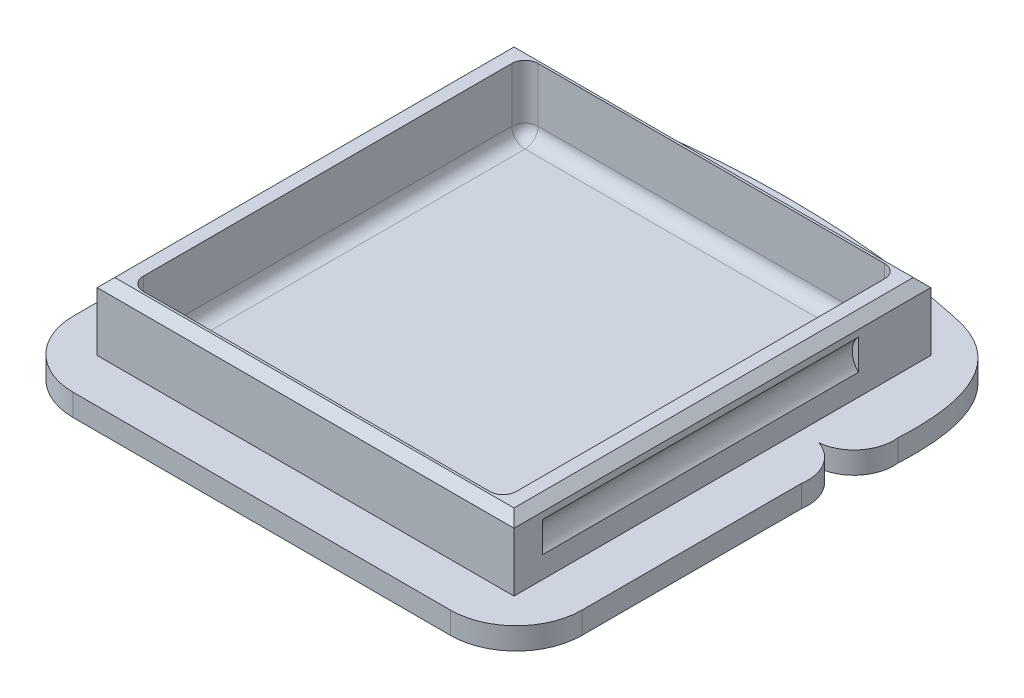
SolidWorks part; units mm, degrees
material "Oak"
ref_plane "Front Plane" through (0, 0, 0) normal (0, 0, 1) x (1, 0, 0)
ref_plane "Top Plane" through (0, 0, 0) normal (0, 1, 0) x (1, 0, 0)
ref_plane "Right Plane" through (0, 0, 0) normal (1, 0, 0) x (0, 0, -1)
sketch "Sketch2" plane through (0, 0, 0) normal (0, 1, 0) x (1, 0, 0)
  line L0 (-66.04, 22.225) -> (66.04, 22.225)
  line L1 (63.5, -66.675) -> (-63.5, -66.675)
  line L2 (63.5, -66.675) -> (63.5, 66.675)
  line L3 (63.5, 66.675) -> (-63.5, 66.675)
  line L4 (-63.5, -66.675) -> (-63.5, 66.675)
  line L5 (63.5, -66.675) -> (-63.5, 66.675) construction
  line L6 (63.5, 66.675) -> (-63.5, -66.675) construction
  line L7 (-73.66, 9.525) -> (-73.66, -53.975)
  line L8 (-54.61, -73.025) -> (54.61, -73.025)
  line L9 (73.66, -53.975) -> (73.66, 9.525)
  line L10 (-73.66, 9.525) -> (-73.66, 13.1711)
  arc A0 (-73.66, 9.525) -> (-66.04, 22.225) centre (-62.3051, 11.348) cw
  arc A1 (73.66, 9.525) -> (66.04, 22.225) centre (62.3051, 11.348) ccw
  arc A2 (-66.04, 22.225) -> (-76.2, 34.925) centre (-64.77, 33.655) cw
  arc A3 (66.04, 22.225) -> (76.2, 34.925) centre (64.77, 33.655) ccw
  arc A4 (-54.2615, 73.3341) -> (54.2615, 73.3341) centre (0, -178.2209) cw
  arc A5 (73.66, -53.975) -> (54.61, -73.025) centre (54.61, -53.975) cw
  arc A6 (-73.66, -53.975) -> (-54.61, -73.025) centre (-54.61, -53.975) ccw
  spline S0 degree 2 poles (-54.2615, 73.3341) (-78.0337, 68.7721) (-76.2, 34.925) knots 0 0 0 1 1 1
  spline S1 degree 2 poles (54.2615, 73.3341) (78.0337, 68.7721) (76.2, 34.925) knots 0 0 0 1 1 1
  point P0 (0, 0)
  dimension "D11" = 11.5003
  dimension "D12" = 11.5003
  dimension "D14" = 11.5003
  dimension "D15" = 11.5003
  dimension "D17" = 19.05
  dimension "D1" = 133.35
  dimension "D2" = 127
  dimension "D3" = 44.45
  dimension "D4" = 2.54
  dimension "D5" = 2.54
  dimension "D6" = 10.16
  dimension "D7" = 10.16
  dimension "D8" = 6.35
  dimension "D9" = 12.7
  dimension "D10" = 12.7
  dimension "D13" = 12.7
extrude "Boss-Extrude1" add sketch "Sketch2" along normal blind 6.35 contours L7 A6 L8 A5 L9 A1 L0 L2 L1 L4 A0 L10 | L4 L1 L2 L0 | L4 L0 L2 | A2 L0 L4 L10 | S1 A4 S0 L10 L4 L3 L2 | L4 L2 L3 | L0 A3 L2 region at (-72.4781, 0, -27.4885) region at (-64.77, 0, -20.4695) region at (0, 0, -44.45) region at (0, 0, 22.225)
sketch "Sketch3" plane through (0, 6.35, 0) normal (0, 1, 0) x (1, 0, 0)
  line L1 (-53.975, 57.15) -> (53.975, 57.15)
  line L2 (-53.975, 57.15) -> (-53.975, -57.15)
  line L3 (-53.975, -57.15) -> (53.975, -57.15)
  line L4 (53.975, 57.15) -> (53.975, -57.15)
  line L5 (-53.975, 57.15) -> (53.975, -57.15) construction
  line L6 (-53.975, -57.15) -> (53.975, 57.15) construction
  line L8 (-60.325, 60.325) -> (60.325, 60.325)
  line L9 (-60.325, 60.325) -> (-60.325, -60.325)
  line L10 (-60.325, -60.325) -> (60.325, -60.325)
  line L11 (60.325, 60.325) -> (60.325, -60.325)
  line L12 (-60.325, 60.325) -> (60.325, -60.325) construction
  line L13 (-60.325, -60.325) -> (60.325, 60.325) construction
  point P0 (0, 0)
  point P10 (0, 0)
  dimension "D1" = 107.95
  dimension "D2" = 114.3
  dimension "D3" = 6.35
  dimension "D4" = 3.175
extrude "Boss-Extrude2" add sketch "Sketch3" along normal blind 19.558
fillet "Fillet2" radius 3.81 4 edges at (53.975, 6.35, 0) (0, 6.35, -57.15) (-53.975, 6.35, 0) (0, 6.35, 57.15)
sketch "Sketch5" plane through (0, 0, 0) normal (0, 0, 1) x (1, 0, 0)
  line L0 (-60.325, 25.908) -> (60.325, 25.908) construction
  line L2 (60.325, 21.4247) -> (60.325, 12.6113)
  line L4 (-60.325, 21.4247) -> (-60.325, 12.6113)
  arc A0 (60.325, 21.4247) -> (60.325, 12.6113) centre (64.897, 17.018) ccw
  arc A1 (-60.325, 21.4247) -> (-60.325, 12.6113) centre (-64.897, 17.018) cw
  dimension "D2" = 12.7
  dimension "D1" = 8.89
  dimension "D3" = 8.89
extrude "Cut-Extrude2" cut sketch "Sketch5" against normal blind 39.37 and the other way blind 52.07
fillet "Fillet3" radius 3.81 8 edges at (52.8591, 7.4659, 56.0341) (52.8591, 7.4659, -56.0341) (-52.8591, 7.4659, -56.0341) (-52.8591, 7.4659, 56.0341) (53.975, 18.034, 57.15) (53.975, 18.034, -57.15) (-53.975, 18.034, -57.15) (-53.975, 18.034, 57.15)
chamfer "Chamfer1" distance 2.54 angle 45 4 edges at (0, 25.908, 60.325) (-60.325, 25.908, 0) (0, 25.908, -60.325) (60.325, 25.908, 0)
